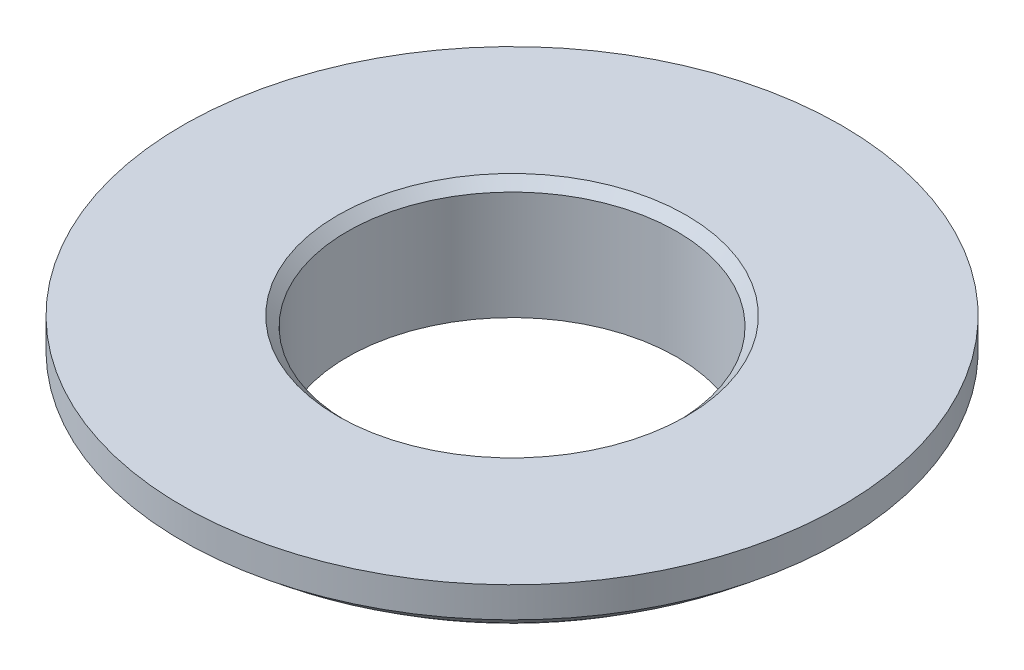
SolidWorks part; units mm, degrees
ref_plane "前视基准面" through (0, 0, 0) normal (0, 0, 1) x (1, 0, 0)
ref_plane "上视基准面" through (0, 0, 0) normal (0, 1, 0) x (1, 0, 0)
ref_plane "右视基准面" through (0, 0, 0) normal (1, 0, 0) x (0, 0, -1)
sketch "草图1" plane through (0, 0, 0) normal (1, 0, 0) x (0, 0, -1)
  line L0 (0, -2.4395) -> (0, 2.4395) construction
  line L1 (-5.25, 2.4395) -> (-10.5, 2.4395)
  line L2 (-10.5, 2.4395) -> (-10.5, 1.4706)
  line L5 (-5.25, -2.4395) -> (0, -2.4395) construction
  line L6 (-5.25, 2.4395) -> (-5.25, -1.5605)
  line L7 (-10.5, 1.4706) -> (-5.25, -1.5605) construction
  arc A0 (-10.5, 1.4706) -> (-5.25, -1.5605) centre (-0.0199, 13.5605) ccw
  point P4 (0, 0)
  dimension "D1" = 21
  dimension "D4" = 16
  dimension "D2" = 10.5
  dimension "D3" = 4
  dimension "D5" = 60
revolve "旋转1" add sketch "草图1" angle 360 about L0
chamfer "倒角1" distance 0.3 angle 45 2 edges at (0, 2.4395, -5.25) (0, -1.5605, -5.25)
